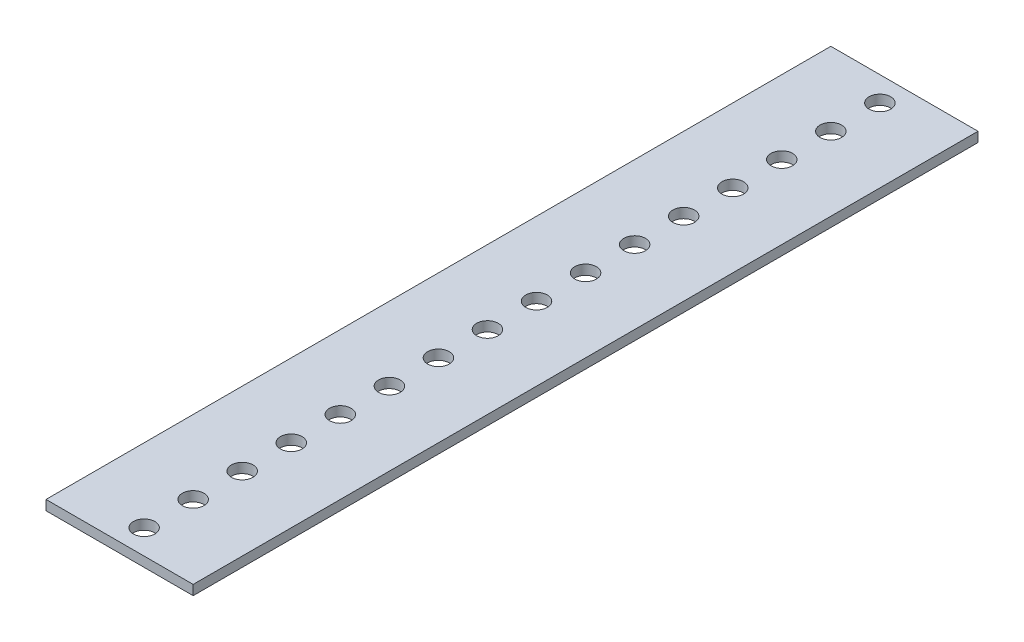
SolidWorks part; units mm, degrees
ref_plane "Front Plane" through (0, 0, 0) normal (0, 0, 1) x (1, 0, 0)
ref_plane "Top Plane" through (0, 0, 0) normal (0, 1, 0) x (1, 0, 0)
ref_plane "Right Plane" through (0, 0, 0) normal (1, 0, 0) x (0, 0, -1)
sketch "Sketch2" plane through (0, 0, 0) normal (0, 1, 0) x (1, 0, 0)
  line L1 (-19.05, -101.6) -> (19.05, -101.6)
  line L2 (-19.05, -101.6) -> (-19.05, 101.6)
  line L3 (-19.05, 101.6) -> (19.05, 101.6)
  line L4 (19.05, -101.6) -> (19.05, 101.6)
  line L5 (-19.05, -101.6) -> (19.05, 101.6) construction
  line L6 (-19.05, 101.6) -> (19.05, -101.6) construction
  point P0 (0, 0)
  dimension "D1" = 38.1
  dimension "D2" = 203.2
extrude "Boss-Extrude1" add sketch "Sketch2" along normal blind 2.54
sketch "Sketch3" plane through (0, 2.54, 0) normal (0, 1, 0) x (1, 0, 0)
  circle A0 centre (0, -95.25) radius 2.794
  point P2 (0, -94.6488)
extrude "Cut-Extrude1" cut sketch "Sketch3" against normal blind 2.54
pattern_linear "LPattern1" count 16 spacing 12.7 along (0, 0, -1) of "Cut-Extrude1"
